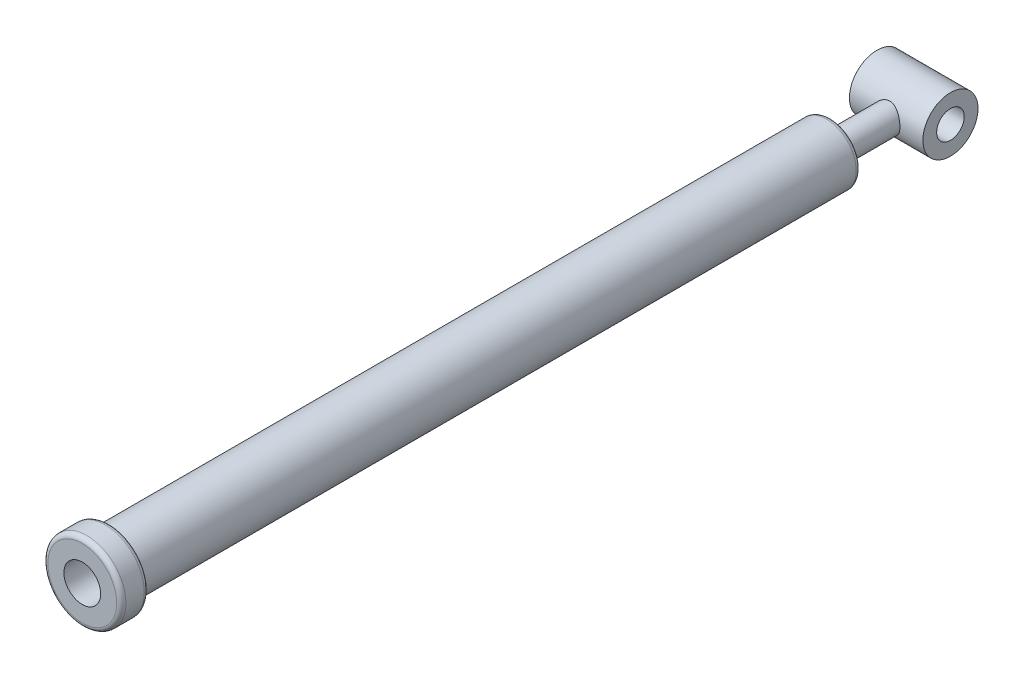
SolidWorks part; units mm, degrees
ref_plane "Front Plane" through (0, 0, 0) normal (0, 0, 1) x (1, 0, 0)
ref_plane "Top Plane" through (0, 0, 0) normal (0, 1, 0) x (1, 0, 0)
ref_plane "Right Plane" through (0, 0, 0) normal (1, 0, 0) x (0, 0, -1)
sketch "Sketch7" plane through (0, 0, 0) normal (0, 0, 1) x (1, 0, 0)
  circle A0 centre (0, 0) radius 20
  circle A1 centre (0, 0) radius 42.5
  dimension "D1" = 85
  dimension "D2" = 40
extrude "Boss-Extrude5" add sketch "Sketch7" against normal blind 30
sketch "Sketch8" plane through (0, 0, -30) normal (0, 0, -1) x (-1, 0, 0)
  circle A0 centre (0, 0) radius 32.5
  circle A1 centre (0, 0) radius 20 construction
  circle A2 centre (0, 0) radius 20
  dimension "D1" = 65
extrude "Boss-Extrude6" add sketch "Sketch8" along normal blind 780
sketch "Sketch9" plane through (0, 0, -810) normal (0, 0, -1) x (-1, 0, 0)
  circle A1 centre (0, 0) radius 32.5
  circle A2 centre (0, 0) radius 32.5
  dimension "D1" = 0
extrude "Boss-Extrude7" add sketch "Sketch9" along normal blind 5
sketch "Sketch10" plane through (0, 0, -815) normal (0, 0, -1) x (-1, 0, 0)
  circle A0 centre (0, 0) radius 15
  dimension "D1" = 30
extrude "Boss-Extrude8" add sketch "Sketch10" along normal blind 65
sketch "Sketch11" plane through (0, 0, 0) normal (1, 0, 0) x (0, 0, -1)
  line L0 (815, -32.5) -> (815, 32.5) construction
  line L1 (880, 0) -> (905, 0) construction
  line L2 (880, -15) -> (880, 15) construction
  circle A0 centre (905, 0) radius 30
  circle A1 centre (905, 0) radius 15
  dimension "D2" = 60
  dimension "D3" = 30
  dimension "D1" = 90
extrude "Boss-Extrude9" add sketch "Sketch11" along normal mid plane 80
fillet "Fillet1" radius 5 3 edges at (42.5, 0, 0) (42.5, 0, -30) (-32.5, 0, -815)
